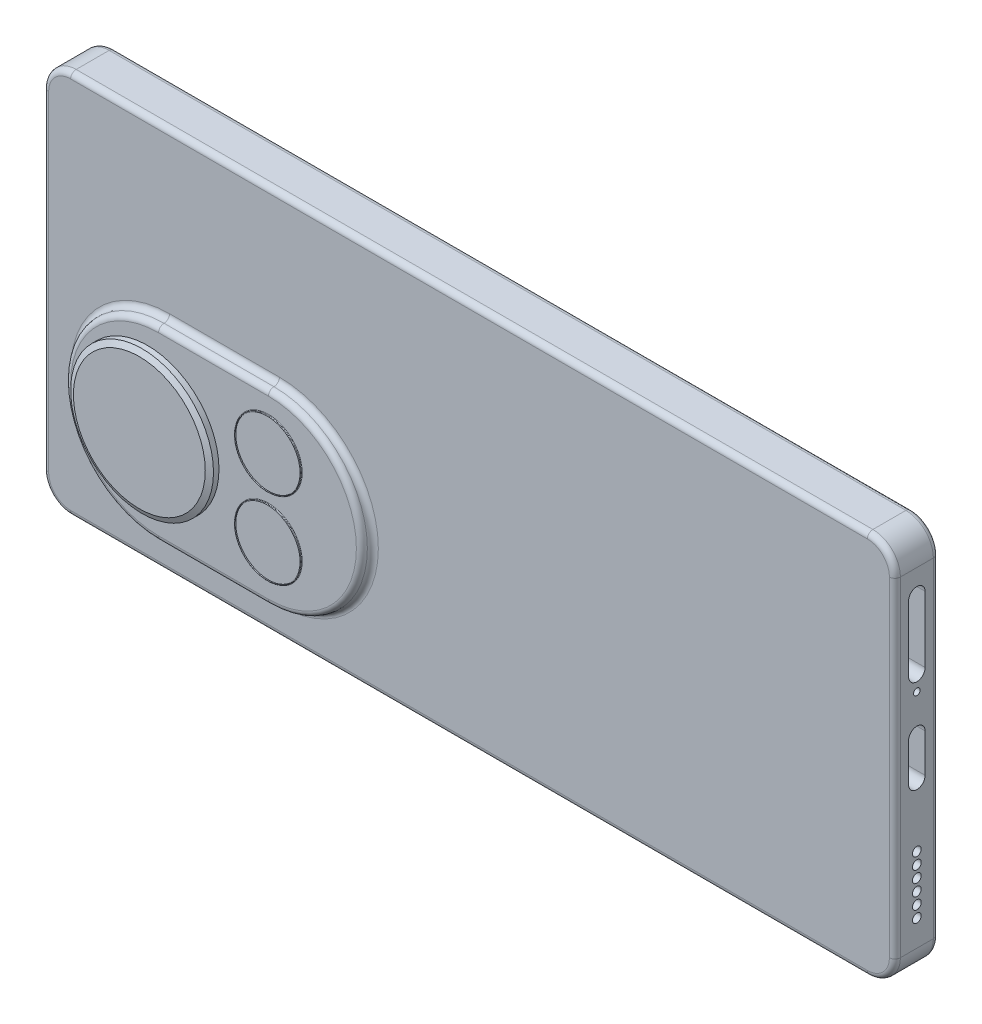
SolidWorks part; units mm, degrees
ref_plane "前视基准面" through (0, 0, 0) normal (0, 0, 1) x (1, 0, 0)
ref_plane "上视基准面" through (0, 0, 0) normal (0, 1, 0) x (1, 0, 0)
ref_plane "右视基准面" through (0, 0, 0) normal (1, 0, 0) x (0, 0, -1)
other "Configuration Table"
sketch "草图1" plane through (0, 0, 0) normal (0, 0, 1) x (1, 0, 0)
  line L0 (-74.792, 32.9786) -> (-74.792, -27.0214)
  line L25 (-69.792, 37.9786) -> (75.208, 37.9786)
  line L26 (80.208, 32.9786) -> (80.208, -27.0214)
  line L27 (-69.792, -32.0214) -> (75.208, -32.0214)
  arc A0 (-69.792, 37.9786) -> (-74.792, 32.9786) centre (-69.792, 32.9786) ccw
  arc A1 (-74.792, -27.0214) -> (-69.792, -32.0214) centre (-69.792, -27.0214) ccw
  arc A2 (75.208, -32.0214) -> (80.208, -27.0214) centre (75.208, -27.0214) ccw
  arc A3 (80.208, 32.9786) -> (75.208, 37.9786) centre (75.208, 32.9786) ccw
  point P6 (-74.792, -27.0214)
  point P16 (-74.792, 32.9786)
  point P17 (-69.792, 37.9786)
  point P18 (75.208, 37.9786)
  point P19 (80.208, 32.9786)
  point P20 (80.208, -27.0214)
  point P21 (75.208, -32.0214)
  point P22 (-69.792, -32.0214)
extrude "凸台-拉伸1" add sketch "草图1" along normal blind 8
fillet "圆角1" radius 1 8 edges at (2.708, 37.9786, 8) (78.7435, 36.5141, 8) (80.208, 2.9786, 8) (78.7435, -30.557, 8) (2.708, -32.0214, 8) (-73.3276, -30.557, 8) (-74.792, 2.9786, 8) (-73.3276, 36.5141, 8)
fillet "圆角2" radius 1 8 edges at (-74.792, 2.9786, 0) (-73.3276, -30.557, 0) (2.708, -32.0214, 0) (78.7435, -30.557, 0) (80.208, 2.9786, 0) (78.7435, 36.5141, 0) (2.708, 37.9786, 0) (-73.3276, 36.5141, 0)
sketch "草图3" plane through (80.208, 0, 0) normal (1, 0, 0) x (0, 0, -1)
  line L2 (-5.5, -0.5214) -> (-5.5, 6.4786)
  line L12 (-2.5, -0.5214) -> (-2.5, 6.4786)
  arc A0 (-5.5, 6.4786) -> (-2.5, 6.4786) centre (-4, 6.4786) cw
  arc A1 (-5.5, -0.5214) -> (-2.5, -0.5214) centre (-4, -0.5214) ccw
  point P10 (-2.5, 6.4786)
  point P14 (-5.5, -0.5214)
extrude "切除-拉伸2" cut sketch "草图3" against normal blind 7 contours L2 A0 L12 A1
sketch "草图6" plane through (73.208, 0, 0) normal (1, 0, 0) x (0, 0, -1)
  line L2 (-4.1, 0.4786) -> (-4.1, 5.4786)
  line L4 (-3.9, 0.4786) -> (-3.9, 5.4786)
  line L5 (-4.1, 0.4786) -> (-3.9, 5.4786) construction
  line L6 (-4.1, 5.4786) -> (-3.9, 0.4786) construction
  arc A0 (-4.1, 5.4786) -> (-3.9, 5.4786) centre (-4, 5.4786) cw
  arc A1 (-4.1, 0.4786) -> (-3.9, 0.4786) centre (-4, 0.4786) ccw
  point P0 (-4, 2.9786)
  point P4 (-4, 2.9786)
  dimension "D1" = 5
  dimension "D2" = 0.2
extrude "凸台-拉伸3" add sketch "草图6" along normal blind 4 contours L2 A0 L4 A1
sketch "草图7" plane through (80.208, 0, 0) normal (1, 0, 0) x (0, 0, -1)
  line L8 (-5.5, 28.4786) -> (-5.5, 16.4786)
  line L10 (-2.5, 28.4786) -> (-2.5, 16.4786)
  arc A5 (-5.5, 16.4786) -> (-2.5, 16.4786) centre (-4, 16.4786) ccw
  arc A6 (-2.5, 28.4786) -> (-5.5, 28.4786) centre (-4, 28.4786) ccw
  dimension "D2" = 3
  dimension "D3" = 12
extrude "切除-拉伸3" cut sketch "草图7" against normal blind 15
sketch "草图8" plane through (80.208, 0, 0) normal (1, 0, 0) x (0, 0, -1)
  circle A3 centre (-4, 13.3786) radius 0.6
  dimension "D2" = 1.2
extrude "切除-拉伸5" cut sketch "草图8" against normal blind 10 contours A3
sketch "草图10" plane through (80.208, 0, 0) normal (1, 0, 0) x (0, 0, -1)
  circle A0 centre (-4, -11.9714) radius 0.95
  dimension "D2" = 1.9
extrude "切除-拉伸6" cut sketch "草图10" against normal blind 10
sketch "草图11" plane through (80.208, 0, 0) normal (1, 0, 0) x (0, 0, -1)
  circle A2 centre (-4, -13.8914) radius 0.85
extrude "切除-拉伸7" cut sketch "草图11" against normal blind 10
sketch "草图12" plane through (80.208, 0, 0) normal (1, 0, 0) x (0, 0, -1)
  circle A1 centre (-4, -11.9714) radius 0.9
  circle A2 centre (-4, -11.9714) radius 0.95
extrude "凸台-拉伸4" add sketch "草图12" against normal blind 10
sketch "草图13" plane through (70.208, 0, 0) normal (1, 0, 0) x (0, 0, -1)
  circle A0 centre (-4, -13.8914) radius 0.85
extrude "凸台-拉伸5" add sketch "草图13" along normal blind 10
sketch "草图14" plane through (80.208, 0, 0) normal (1, 0, 0) x (0, 0, -1)
  circle A2 centre (-4, -13.9914) radius 0.9
extrude "切除-拉伸8" cut sketch "草图14" against normal blind 10
sketch "草图15" plane through (80.208, 0, 0) normal (1, 0, 0) x (0, 0, -1)
  circle A0 centre (-4, -11.9714) radius 0.8
  circle A1 centre (-4, -11.9714) radius 0.9
extrude "凸台-拉伸6" add sketch "草图15" against normal blind 10
sketch "草图16" plane through (70.208, 0, 0) normal (1, 0, 0) x (0, 0, -1)
  circle A0 centre (-4, -13.9914) radius 0.8
  circle A1 centre (-4, -13.9914) radius 0.9
extrude "凸台-拉伸7" add sketch "草图16" along normal blind 10
sketch "草图17" plane through (70.208, 0, 0) normal (1, 0, 0) x (0, 0, -1)
  circle A0 centre (-4, -11.9714) radius 0.8
extrude "凸台-拉伸8" add sketch "草图17" along normal blind 10
sketch "草图18" plane through (70.208, 0, 0) normal (1, 0, 0) x (0, 0, -1)
  circle A0 centre (-4, -13.9914) radius 0.8
extrude "凸台-拉伸9" add sketch "草图18" along normal blind 10
sketch "草图19" plane through (80.208, 0, 0) normal (1, 0, 0) x (0, 0, -1)
  circle A1 centre (-4, -11.7714) radius 0.8
  point P10 (-4, -17.0214)
extrude "切除-拉伸9" cut sketch "草图19" against normal blind 10
sketch "草图20" plane through (80.208, 0, 0) normal (1, 0, 0) x (0, 0, -1)
  circle A1 centre (-4, -13.8714) radius 0.8
extrude "切除-拉伸10" cut sketch "草图20" against normal blind 10 contours A1
sketch "草图21" plane through (80.208, 0, 0) normal (1, 0, 0) x (0, 0, -1)
  circle A1 centre (-4, -15.9714) radius 0.8
extrude "切除-拉伸11" cut sketch "草图21" against normal blind 10
sketch "草图22" plane through (80.208, 0, 0) normal (1, 0, 0) x (0, 0, -1)
  circle A2 centre (-4, -18.0714) radius 0.8
extrude "切除-拉伸12" cut sketch "草图22" against normal blind 10
sketch "草图23" plane through (80.208, 0, 0) normal (1, 0, 0) x (0, 0, -1)
  circle A2 centre (-4, -20.1714) radius 0.8
extrude "切除-拉伸13" cut sketch "草图23" against normal blind 10
sketch "草图24" plane through (80.208, 0, 0) normal (1, 0, 0) x (0, 0, -1)
  circle A3 centre (-4, -22.2714) radius 0.8
extrude "切除-拉伸14" cut sketch "草图24" against normal blind 10
sketch "草图25" plane through (0, 37.9786, 0) normal (0, 1, 0) x (1, 0, 0)
  line L4 (-14.792, -5) -> (-31.792, -5)
  line L6 (-14.792, -3) -> (-31.792, -3)
  arc A0 (-31.792, -3) -> (-31.792, -5) centre (-31.792, -4) ccw
  arc A1 (-14.792, -3) -> (-14.792, -5) centre (-14.792, -4) cw
  point P4 (-23.292, -4)
  dimension "D3" = 2
extrude "切除-拉伸15" cut sketch "草图25" against normal blind 1 contours L4 A0 L6 A1
sketch "草图26" plane through (0, 37.9786, 0) normal (0, 1, 0) x (1, 0, 0)
  line L2 (-6.792, -5) -> (0.208, -5)
  line L4 (-6.792, -3) -> (0.208, -3)
  line L6 (-6.792, -5) -> (0.208, -3) construction
  line L7 (-6.792, -3) -> (0.208, -5) construction
  arc A0 (-6.792, -3) -> (-6.792, -5) centre (-6.792, -4) ccw
  arc A1 (0.208, -5) -> (0.208, -3) centre (0.208, -4) ccw
  dimension "D2" = 2
  dimension "D3" = 7
extrude "切除-拉伸16" cut sketch "草图26" against normal blind 1
sketch "草图28" plane through (0, 37.9786, 0) normal (0, 1, 0) x (1, 0, 0)
  line L0 (-31.792, -3) -> (-14.792, -3)
  line L1 (-14.792, -5) -> (-31.792, -5)
  arc A0 (-14.792, -5) -> (-14.792, -3) centre (-14.792, -4) ccw construction
  arc A1 (-14.792, -5) -> (-14.792, -3) centre (-14.792, -4) ccw construction
  arc A2 (-31.792, -3) -> (-31.792, -5) centre (-31.792, -4) ccw
  arc A3 (-14.792, -5) -> (-14.792, -3) centre (-14.792, -4) ccw
extrude "切除-拉伸17" cut sketch "草图28" against normal blind 128
sketch "草图30" plane through (0, 37.9786, 0) normal (0, 1, 0) x (1, 0, 0)
  line L0 (-6.792, -3) -> (0.208, -3)
  line L1 (0.208, -5) -> (-6.792, -5)
  arc A0 (-6.792, -3) -> (-6.792, -5) centre (-6.792, -4) ccw construction
  arc A1 (-6.792, -3) -> (-6.792, -5) centre (-6.792, -4) ccw construction
  arc A2 (-6.792, -3) -> (-6.792, -5) centre (-6.792, -4) ccw
  arc A3 (0.208, -5) -> (0.208, -3) centre (0.208, -4) ccw
extrude "切除-拉伸18" cut sketch "草图30" against normal blind 128
sketch "草图32" plane through (0, 37.9786, 0) normal (0, 1, 0) x (1, 0, 0)
  line L0 (-31.792, -3) -> (-14.792, -3)
  line L1 (-14.792, -5) -> (-31.792, -5)
  arc A0 (-31.792, -5) -> (-31.792, -3) centre (-31.792, -4) cw
  arc A1 (-14.792, -3) -> (-14.792, -5) centre (-14.792, -4) cw
extrude "凸台-拉伸10" add sketch "草图32" against normal blind 69
sketch "草图33" plane through (0, 37.9786, 0) normal (0, 1, 0) x (1, 0, 0)
  line L0 (-6.792, -3) -> (0.208, -3)
  line L1 (0.208, -5) -> (-6.792, -5)
  line L2 (-6.792, -5) -> (0.208, -5) construction
  arc A0 (0.208, -5) -> (0.208, -3) centre (0.208, -4) ccw construction
  arc A1 (-6.792, -5) -> (-6.792, -3) centre (-6.792, -4) cw
  arc A2 (0.208, -5) -> (0.208, -3) centre (0.208, -4) ccw
extrude "凸台-拉伸12" add sketch "草图33" against normal blind 69 contours L1 A1 L0 A2
sketch "草图34" plane through (80.208, 0, 0) normal (1, 0, 0) x (0, 0, -1)
  circle A0 centre (-4, -22.2714) radius 0.8
extrude "切除-拉伸19" cut sketch "草图34" against normal blind 190
sketch "草图37" plane through (-74.792, 0, 0) normal (-1, 0, 0) x (0, 0, 1)
  circle A0 centre (4, -22.2714) radius 0.6
  circle A1 centre (4, -22.2714) radius 0.8
extrude "凸台-拉伸13" add sketch "草图37" against normal blind 10
sketch "草图39" plane through (-64.792, 0, 0) normal (1, 0, 0) x (0, 0, -1)
  circle A0 centre (-4, -22.2714) radius 0.8
extrude "凸台-拉伸14" add sketch "草图39" along normal blind 135
sketch "草图40" plane through (73.208, 0, 0) normal (1, 0, 0) x (0, 0, -1)
  circle A0 centre (-4, 0.4786) radius 0.6
extrude "切除-拉伸20" cut sketch "草图40" against normal blind 155
sketch "草图43" plane through (73.208, 0, 0) normal (-1, 0, 0) x (0, 0, 1)
  circle A0 centre (4, 0.4786) radius 0.6
extrude "凸台-拉伸15" add sketch "草图43" along normal blind 145
sketch "草图44" plane through (-74.792, 0, 0) normal (-1, 0, 0) x (0, 0, 1)
  circle A2 centre (4, 2.6786) radius 0.6
extrude "切除-拉伸21" cut sketch "草图44" against normal blind 10
sketch "草图45" plane through (-74.792, 0, 0) normal (-1, 0, 0) x (0, 0, 1)
  circle A2 centre (4, 4.8786) radius 0.6
extrude "切除-拉伸22" cut sketch "草图45" against normal blind 10
sketch "草图47" plane through (0, -32.0214, 0) normal (0, -1, 0) x (1, 0, 0)
  circle A0 centre (-14.792, 4) radius 1
extrude "凸台-拉伸16" add sketch "草图47" along normal blind 10 separate body
sketch "草图49" plane through (0, -42.0214, 0) normal (0, -1, 0) x (1, 0, 0)
  circle A0 centre (-14.792, 4) radius 1
extrude "切除-拉伸23" cut sketch "草图49" against normal blind 10
sketch "草图50" plane through (0, -31.0214, 0) normal (0, -1, 0) x (1, 0, 0)
  circle A0 centre (-31.792, 4) radius 1
extrude "凸台-拉伸17" add sketch "草图50" along normal blind 10
sketch "草图53" plane through (0, 0, 8) normal (0, 0, 1) x (1, 0, 0)
  line L3 (-31.792, -26.0214) -> (-51.792, -26.0214)
  line L5 (-31.792, 7.9786) -> (-51.792, 7.9786)
  arc A0 (-51.792, 7.9786) -> (-51.792, -26.0214) centre (-51.792, -9.0214) ccw
  arc A1 (-31.792, -26.0214) -> (-31.792, 7.9786) centre (-31.792, -9.0214) ccw
  dimension "D2" = 34
  dimension "D3" = 20
extrude "凸台-拉伸18" add sketch "草图53" along normal blind 2
fillet "圆角3" radius 1 4 edges at (-68.792, -9.0214, 8) (-41.792, -26.0214, 8) (-14.792, -9.0214, 8) (-41.792, 7.9786, 8)
fillet "圆角4" radius 1 4 edges at (-41.792, -26.0214, 10) (-68.792, -9.0214, 10) (-41.792, 7.9786, 10) (-14.792, -9.0214, 10)
sketch "草图54" plane through (0, 0, 10) normal (0, 0, 1) x (1, 0, 0)
  circle A4 centre (-53.792, -9.0214) radius 13
  dimension "D2" = 26
extrude "凸台-拉伸19" add sketch "草图54" along normal blind 1
sketch "草图55" plane through (0, 0, 11) normal (0, 0, 1) x (1, 0, 0)
  circle A0 centre (-53.792, -9.0214) radius 12
extrude "凸台-拉伸20" add sketch "草图55" along normal blind 0.5
loft "放样1" add section edge at (-41.792, -9.0214, 11.5) section edge at (-40.792, -9.0214, 11) connector at (-65.7502, -8.0198, 11.5) connector at (-66.7809, -8.4825, 11)
sketch "草图56" plane through (0, -41.0214, 0) normal (0, -1, 0) x (1, 0, 0)
  circle A0 centre (-31.792, 4) radius 1
extrude "切除-拉伸24" cut sketch "草图56" against normal blind 10
sketch "草图57" plane through (0, 0, 10) normal (0, 0, 1) x (1, 0, 0)
  circle A4 centre (-31.792, -16.0214) radius 6.05
  circle A5 centre (-31.792, -16.0214) radius 5.95
extrude "凸台-拉伸21" add sketch "草图57" along normal blind 0.2
fillet "圆角6" radius 0.1 2 edges at (-25.742, -16.0214, 10) (-25.742, -16.0214, 10.2)
sketch "草图58" plane through (0, 0, 10) normal (0, 0, 1) x (1, 0, 0)
  circle A0 centre (-31.792, -2.0214) radius 6.05
  circle A1 centre (-31.792, -2.0214) radius 5.95
extrude "凸台-拉伸22" add sketch "草图58" along normal blind 0.2
fillet "圆角9" radius 0.1 2 edges at (-25.742, -2.0214, 10) (-25.742, -2.0214, 10.2)
sketch "草图61" plane through (-64.792, 0, 0) normal (-1, 0, 0) x (0, 0, 1)
  circle A0 centre (4, 4.8786) radius 0.6
extrude "凸台-拉伸23" add sketch "草图61" along normal blind 10
sketch "草图62" plane through (-64.792, 0, 0) normal (-1, 0, 0) x (0, 0, 1)
  circle A0 centre (4, 2.6786) radius 0.6
extrude "凸台-拉伸24" add sketch "草图62" along normal blind 10
sketch "草图65" plane through (-74.792, 0, 0) normal (-1, 0, 0) x (0, 0, 1)
  circle A0 centre (4, 0.4786) radius 0.6
extrude "凸台-拉伸28" add sketch "草图65" against normal blind 20
sketch "草图67" plane through (-74.792, 0, 0) normal (-1, 0, 0) x (0, 0, 1)
  circle A0 centre (4, 9.5786) radius 0.6
extrude "切除-拉伸26" cut sketch "草图67" against normal blind 10
sketch "草图68" plane through (-74.792, 0, 0) normal (-1, 0, 0) x (0, 0, 1)
  circle A2 centre (4, 11.7786) radius 0.6
extrude "切除-拉伸27" cut sketch "草图68" against normal blind 10
sketch "草图69" plane through (-74.792, 0, 0) normal (-1, 0, 0) x (0, 0, 1)
  circle A2 centre (4, 13.9786) radius 0.6
extrude "切除-拉伸28" cut sketch "草图69" against normal blind 10
